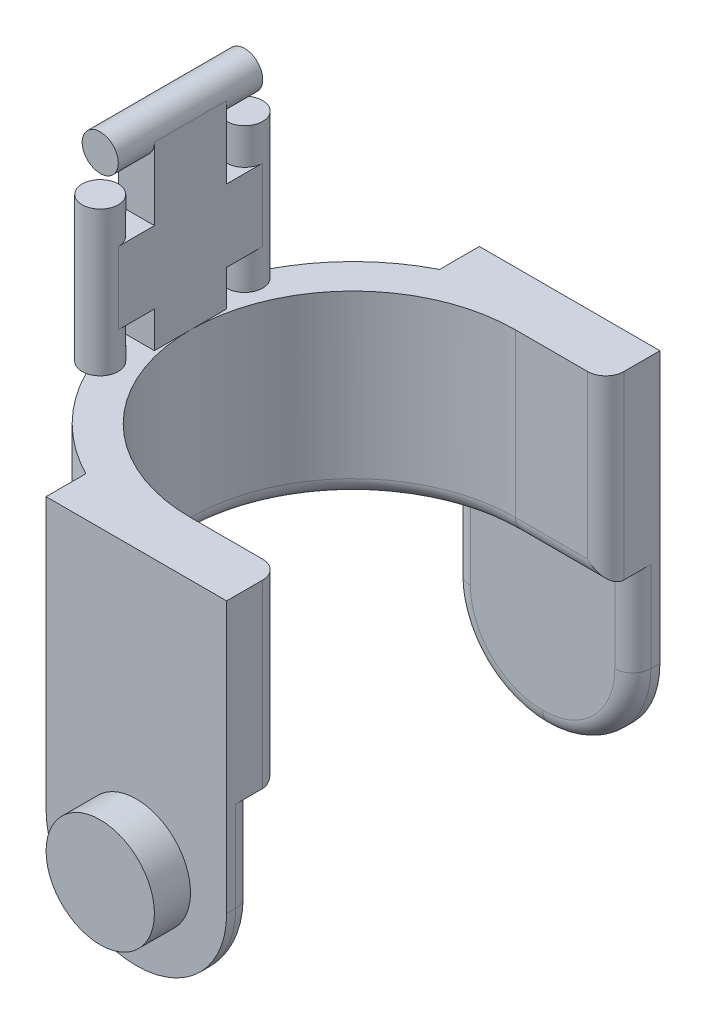
SolidWorks part; units mm, degrees
ref_plane "Front Plane" through (0, 0, 0) normal (0, 0, 1) x (1, 0, 0)
ref_plane "Top Plane" through (0, 0, 0) normal (0, 1, 0) x (1, 0, 0)
ref_plane "Right Plane" through (0, 0, 0) normal (1, 0, 0) x (0, 0, -1)
sketch "Sketch1" plane through (0, 0, 0) normal (0, 1, 0) x (1, 0, 0)
  line L0 (0, 55) -> (0, 45)
  line L1 (0, -45) -> (0, -55)
  arc A0 (0, -45) -> (0, 45) centre (0, 0) cw
  arc A1 (0, -55) -> (0, 55) centre (0, 0) cw
  dimension "D1" = 45
  dimension "D2" = 55
extrude "Boss-Extrude1" add sketch "Sketch1" along normal blind 50
sketch "Sketch2" plane through (0, 0, 0) normal (0, 1, 0) x (1, 0, 0)
  line L0 (25, -45) -> (25, -60)
  line L1 (25, -45) -> (-25, -45)
  line L2 (0, -55) -> (0, -45) construction
  line L3 (25, -60) -> (-25, -60)
  line L4 (-25, -45) -> (-25, -60)
  dimension "D1" = 50
  dimension "D2" = 15
  dimension "D3" = 25
  dimension "D4" = 5
extrude "Boss-Extrude2" add sketch "Sketch2" along normal blind 50
sketch "Sketch3" plane through (0, 0, 0) normal (0, -1, 0) x (1, 0, 0)
  line L0 (25, 60) -> (25, 45) construction
  line L1 (-25, 60) -> (25, 60)
  line L2 (-25, 60) -> (-25, 52.5)
  line L3 (-25, 52.5) -> (25, 52.5)
  line L4 (25, 60) -> (25, 52.5)
extrude "Boss-Extrude3" add sketch "Sketch3" along normal blind 50
sketch "Sketch4" plane through (0, 0, 60) normal (0, 0, 1) x (1, 0, 0)
  line L0 (25, -50) -> (-25, -50) construction
  line L1 (25, 50) -> (25, -50) construction
  circle A0 centre (0, -25) radius 15
  dimension "D1" = 30
  dimension "D2" = 25
  dimension "D3" = 25
extrude "Boss-Extrude4" add sketch "Sketch4" along normal blind 10
fillet "Fillet1" radius 25 2 edges at (-25, -50, 56.25) (25, -50, 56.25)
mirror "Mirror1" about plane through (0, 0, 0) normal (0, 0, 1) of "Boss-Extrude4", "Boss-Extrude3", "Boss-Extrude2", "Fillet1"
fillet "Fillet2" radius 5 14 edges at (-25, -12.5, -52.5) (-17.6777, -42.6777, -52.5) (17.6777, -42.6777, -52.5) (-17.6777, -42.6777, 52.5) (17.6777, -42.6777, 52.5) (12.5, 0, 45) (12.5, 0, -45) (-55, 0, 0) (25, -12.5, -52.5) (-45, 0, 0) (25, 25, 45) (25, 25, -45)
sketch "Sketch5" plane through (0, 50, 0) normal (0, 1, 0) x (1, 0, 0)
  line L1 (-45, 0) -> (-55, 0)
  line L2 (-45, 0) -> (-45, -10)
  line L3 (-45, -10) -> (-55, -10)
  line L4 (-55, 0) -> (-55, -10)
  arc A0 (0, 45) -> (0, -45) centre (0, 0) ccw construction
  dimension "D1" = 10
extrude "Boss-Extrude5" add sketch "Sketch5" along normal blind 40
sketch "Sketch6" plane through (0, 0, 10) normal (0, 0, 1) x (1, 0, 0)
  line L0 (-45, 90) -> (-45, 50) construction
  line L1 (-45, 80) -> (-55, 80)
  line L2 (-45, 80) -> (-45, 60)
  line L3 (-45, 60) -> (-55, 60)
  line L4 (-55, 80) -> (-55, 60)
  line L5 (-55, 90) -> (-55, 50) construction
  line L6 (-54.0833, 50) -> (-45, 50) construction
  dimension "D1" = 20
  dimension "D2" = 10
extrude "Boss-Extrude6" add sketch "Sketch6" along normal blind 10
sketch "Sketch7" plane through (0, 80, 0) normal (0, 1, 0) x (1, 0, 0)
  line L0 (-45, -20) -> (-55, -20) construction
  circle A0 centre (-50, -20) radius 5
  dimension "D1" = 10
extrude "Boss-Extrude7" add sketch "Sketch7" along normal blind 10 and the other way blind 30
mirror "Mirror2" about plane through (-45, 90, 0) normal (0, 0, 1) of "Boss-Extrude7", "Boss-Extrude6", "Boss-Extrude5"
sketch "Sketch8" plane through (0, 90, 0) normal (0, 1, 0) x (1, 0, 0)
  line L1 (-55, 10) -> (-45, 10)
  line L2 (-55, 10) -> (-55, -10)
  line L3 (-55, -10) -> (-45, -10)
  line L4 (-45, 10) -> (-45, -10)
extrude "Boss-Extrude8" add sketch "Sketch8" along normal blind 10
sketch "Sketch9" plane through (0, 0, 0) normal (0, 0, 1) x (1, 0, 0)
  line L0 (-55, 100) -> (-45, 100) construction
  circle A0 centre (-50, 100) radius 5
extrude "Boss-Extrude9" add sketch "Sketch9" along normal blind 20 and the other way blind 20
